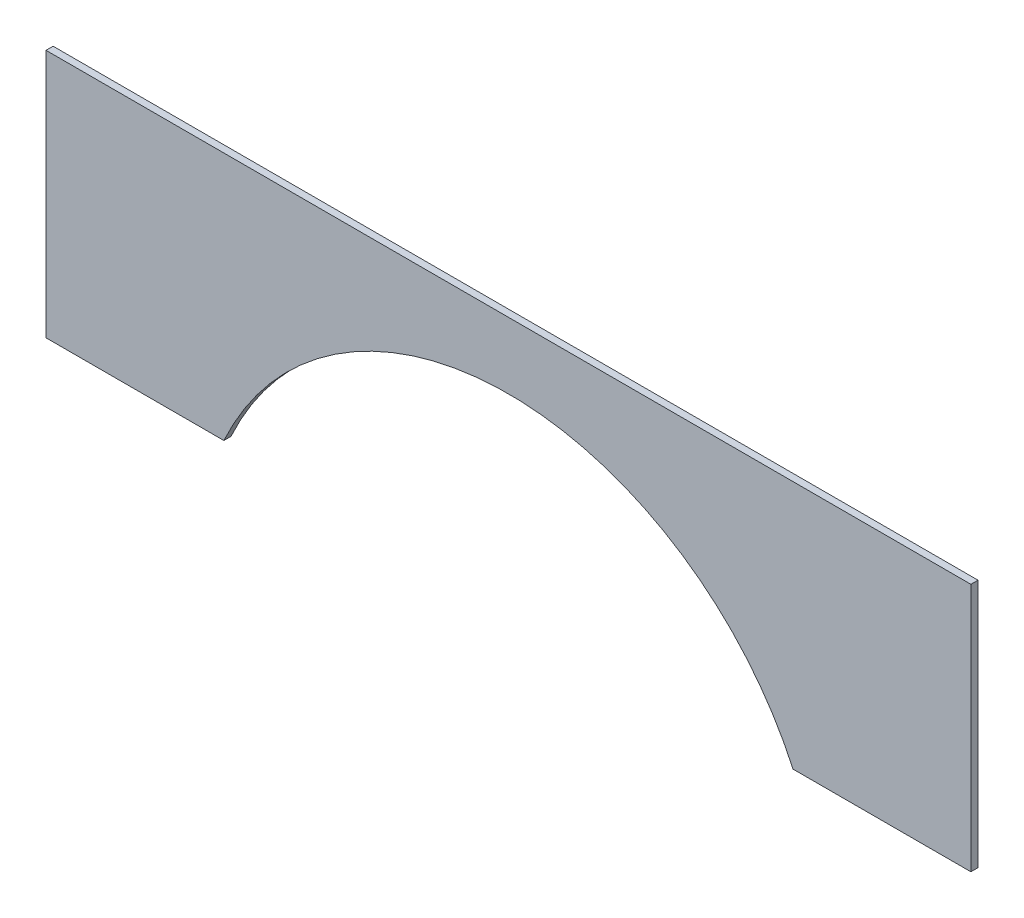
SolidWorks part; units mm, degrees
ref_plane "Front Plane" through (0, 0, 0) normal (0, 0, 1) x (1, 0, 0)
ref_plane "Top Plane" through (0, 0, 0) normal (0, 1, 0) x (1, 0, 0)
ref_plane "Right Plane" through (0, 0, 0) normal (1, 0, 0) x (0, 0, -1)
sketch "Sketch1" plane through (0, 0, 0) normal (0, 0, 1) x (1, 0, 0)
  line L0 (0, 0) -> (63.5, 0)
  line L2 (0, 0) -> (0, 88.9)
  line L3 (0, 88.9) -> (330.2, 88.9)
  line L4 (330.2, 0) -> (330.2, 88.9)
  line L5 (330.2, 0) -> (266.7, 0)
  arc A1 (63.5, 0) -> (266.7, 0) centre (165.1, -46.4889) cw
  dimension "D1" = 330.2
  dimension "D2" = 88.9
  dimension "D3" = 203.2
extrude "Boss-Extrude1" add sketch "Sketch1" along normal blind 2.54 contours A1 L5 L4 L3 L2 L0
